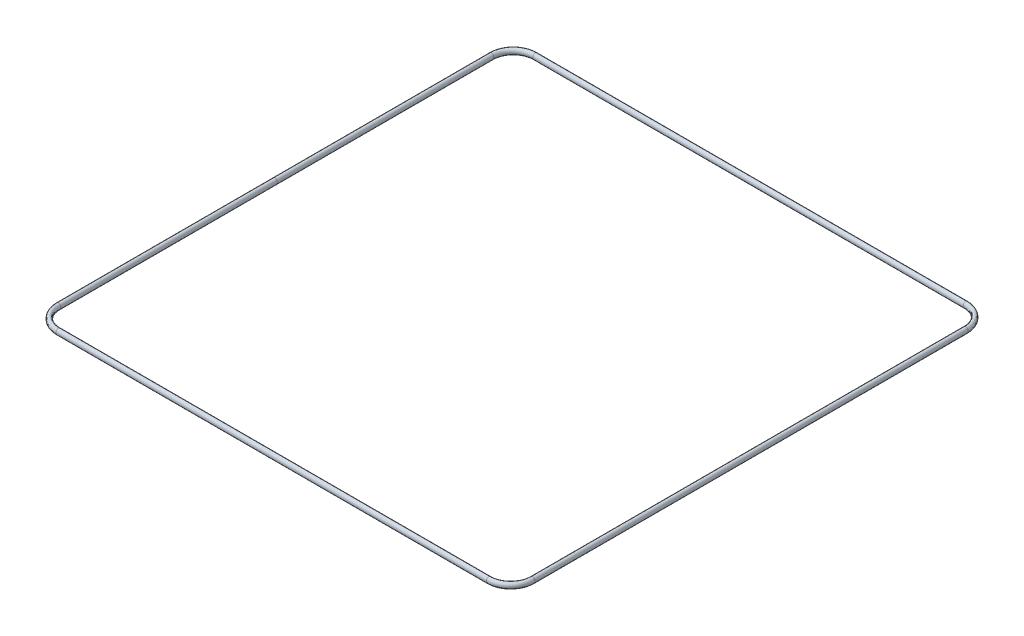
SolidWorks part; units mm, degrees
material "Rubber"
ref_plane "Front Plane" through (0, 0, 0) normal (0, 0, 1) x (1, 0, 0)
ref_plane "Top Plane" through (0, 0, 0) normal (0, 1, 0) x (1, 0, 0)
ref_plane "Right Plane" through (0, 0, 0) normal (1, 0, 0) x (0, 0, -1)
sketch "Sketch1" plane through (0, 0, 0) normal (0, 1, 0) x (1, 0, 0)
  line L1 (-127.381, -141.097) -> (127.381, -141.097)
  line L2 (-140.335, -128.143) -> (-140.335, 128.143)
  line L3 (-127.381, 141.097) -> (127.381, 141.097)
  line L4 (140.335, -128.143) -> (140.335, 128.143)
  line L5 (-140.335, -141.097) -> (140.335, 141.097) construction
  line L6 (-140.335, 141.097) -> (140.335, -141.097) construction
  arc A0 (127.381, 141.097) -> (140.335, 128.143) centre (127.381, 128.143) cw
  arc A1 (127.381, -141.097) -> (140.335, -128.143) centre (127.381, -128.143) ccw
  arc A2 (-127.381, -141.097) -> (-140.335, -128.143) centre (-127.381, -128.143) cw
  arc A3 (-140.335, 128.143) -> (-127.381, 141.097) centre (-127.381, 128.143) cw
  point P0 (0, 0)
  dimension "D3" = 12.954
  dimension "D1" = 280.67
  dimension "D2" = 282.194
sketch "Sketch44" plane through (0, 0, 0) normal (0, 0, 1) x (1, 0, 0)
  line L0 (-140.335, 0) -> (140.335, 0) construction
  line L1 (-127.381, 0) -> (-140.335, 0) construction
  ellipse E0 centre (-140.335, 0) end of major axis (-140.335, 1.78) minor radius 1.397
  point P1 (-143.383, 1.78)
  point P7 (0, 0)
  dimension "D1" = 3.56
  dimension "D2" = 2.794
sweep "Sweep2" add profiles "Sketch44" path "Sketch1"
